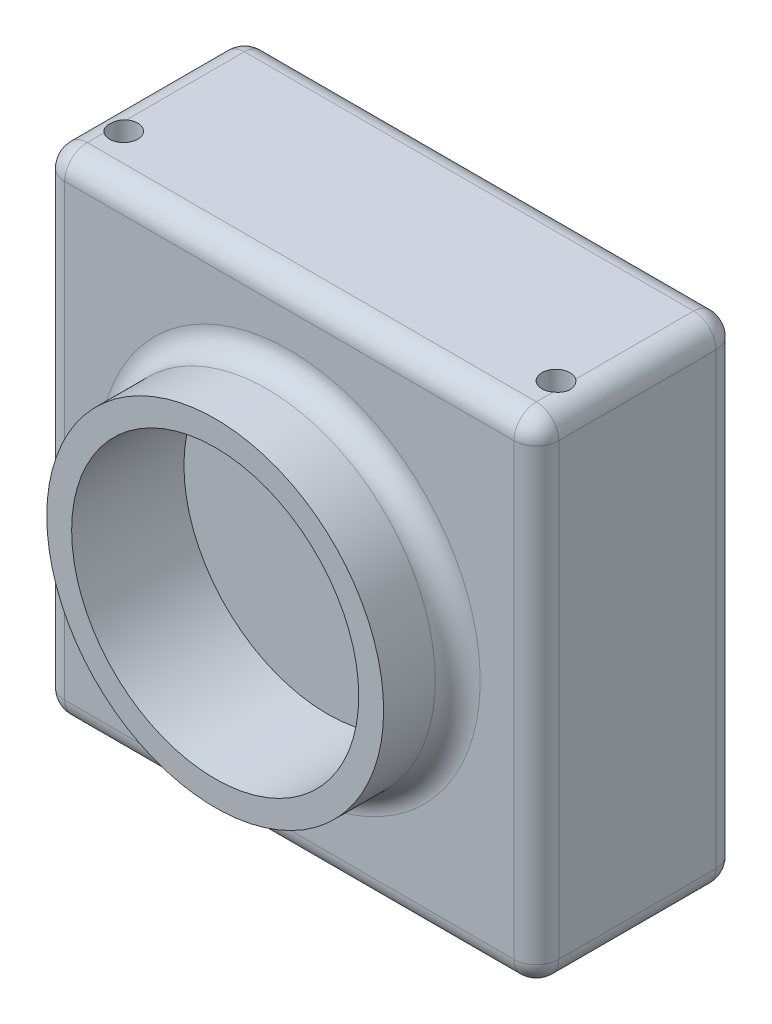
SolidWorks part; units mm, degrees
ref_plane "Front Plane" through (0, 0, 0) normal (0, 0, 1) x (1, 0, 0)
ref_plane "Top Plane" through (0, 0, 0) normal (0, 1, 0) x (1, 0, 0)
ref_plane "Right Plane" through (0, 0, 0) normal (1, 0, 0) x (0, 0, -1)
sketch "Sketch1" plane through (0, 0, 0) normal (0, 0, 1) x (1, 0, 0)
  line L1 (-22, -22) -> (22, -22)
  line L2 (-22, -22) -> (-22, 22)
  line L3 (-22, 22) -> (22, 22)
  line L4 (22, -22) -> (22, 22)
  line L5 (-22, -22) -> (22, 22) construction
  line L6 (-22, 22) -> (22, -22) construction
  point P0 (0, 0)
  dimension "D1" = 44
  dimension "D2" = 44
extrude "Boss-Extrude1" add sketch "Sketch1" along normal blind 18
sketch "Sketch2" plane through (0, 0, 18) normal (0, 0, 1) x (1, 0, 0)
  circle A0 centre (0, 0) radius 15
  dimension "D1" = 30
extrude "Boss-Extrude2" add sketch "Sketch2" along normal blind 6.6
hole_wizard "M3 Tapped Hole1" positions "Sketch3" profile "Sketch4" tap size "M3" standard "DIN"
sketch "Sketch3" plane through (0, 22, 0) normal (0, 1, 0) x (1, 0, 0)
  line L0 (0, 0) -> (0, -19.0128) construction
  line L1 (22, 0) -> (-22, 0) construction
  line L2 (-15, -24.6) -> (15, -24.6) construction
  point P0 (-19.25, -13.5)
  point P12 (19.25, -13.5)
  dimension "D1" = 38.5
  dimension "D2" = 11.1
sketch "Sketch4" plane through (-19.25, 22, 13.5) normal (1, 0, 0) x (0, 0, 1)
  line L0 (0, 0) -> (0, 8.2511)
  line L1 (0, 8.2511) -> (1.25, 7.5)
  line L2 (1.25, 7.5) -> (1.25, 0)
  line L5 (1.25, 0) -> (0, 0)
  line L10 (0, 8.2511) -> (-1.25, 7.5) construction
  line L11 (0, -6.35) -> (0, 107.95) construction
  dimension "Tap Drill Dia." = 2.5
  dimension "Tap Drill Depth" = 7.5
  dimension "Drill Angle" = 118
cosmetic thread "Hole Thread1" parameters "D1"=6, "D2"=3
cosmetic thread "Hole Thread2" parameters "D1"=6, "D2"=3
sketch "Sketch5" plane through (0, 0, 0) normal (0, 0, -1) x (-1, 0, 0)
  line L0 (0, 22) -> (0, -13) construction
  line L1 (-22, 22) -> (22, 22) construction
  line L2 (22, -22) -> (-22, -22) construction
  circle A0 centre (0, -13) radius 4
  dimension "D1" = 8
  dimension "D2" = 9
extrude "Boss-Extrude3" add sketch "Sketch5" along normal blind 3.4
fillet "Fillet2" radius 2 13 edges at (0, -22, 18) (-22, 0, 18) (0, 22, 18) (22, 0, 18) (15, 0, 18) (22, 0, 0) (0, -22, 0) (-22, 0, 0) (0, 22, 0) (22, -22, 9) (-22, -22, 9) (22, 22, 9) (-22, 22, 9)
sketch "Sketch6" plane through (0, 0, 24.6) normal (0, 0, 1) x (1, 0, 0)
  circle A0 centre (0, 0) radius 12.7842
extrude "Cut-Extrude1" cut sketch "Sketch6" against normal blind 10
